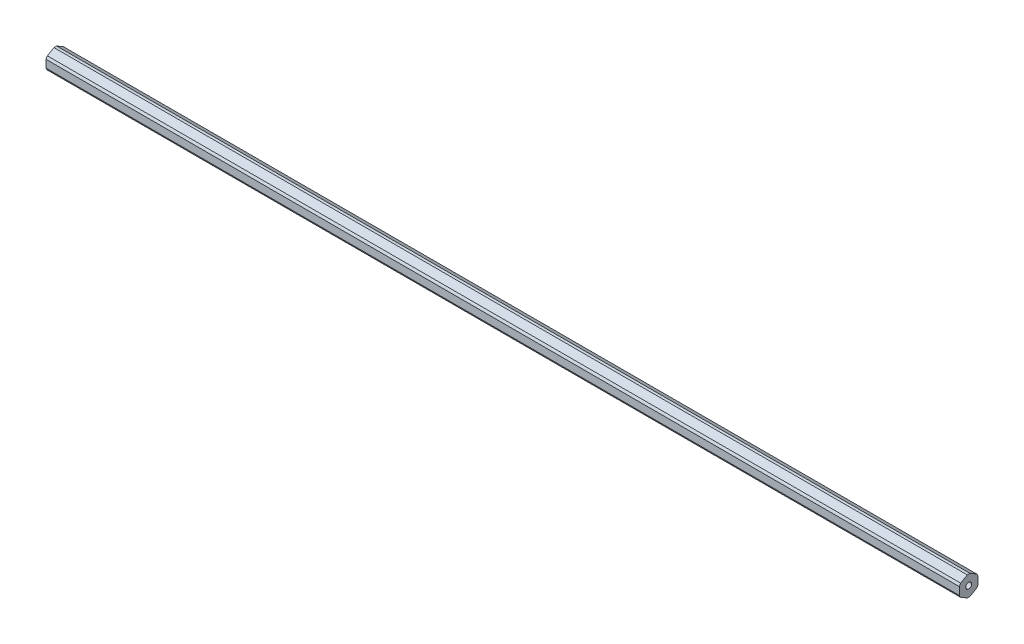
SolidWorks part; units mm, degrees
material "6061 Alloy"
ref_plane "Front Plane" through (0, 0, 0) normal (0, 0, 1) x (1, 0, 0)
ref_plane "Top Plane" through (0, 0, 0) normal (0, 1, 0) x (1, 0, 0)
ref_plane "Right Plane" through (0, 0, 0) normal (1, 0, 0) x (0, 0, -1)
ref_plane "Plane1" through (914.4, 0, 0) normal (1, 0, 0) x (0, 0, -1)
sketch "Sketch1" plane through (914.4, 0, 0) normal (1, 0, 0) x (0, 0, -1)
  line L0 (-5.4343, -4.1949) -> (-0.9157, -6.8037)
  line L1 (0.9157, -6.8037) -> (5.4343, -4.1949)
  line L2 (6.35, -2.6088) -> (6.35, 2.6088)
  line L3 (5.4343, 4.1949) -> (0.9157, 6.8037)
  line L4 (-0.9157, 6.8037) -> (-5.4343, 4.1949)
  line L5 (-6.35, 2.6088) -> (-6.35, -2.6088)
  circle A0 centre (0, 0) radius 1.9939
  arc A1 (-6.35, -2.6088) -> (-5.4343, -4.1949) centre (0, 0) ccw
  arc A2 (-0.9157, -6.8037) -> (0.9157, -6.8037) centre (0, 0) ccw
  arc A3 (5.4343, -4.1949) -> (6.35, -2.6088) centre (0, 0) ccw
  arc A4 (6.35, 2.6088) -> (5.4343, 4.1949) centre (0, 0) ccw
  arc A5 (0.9157, 6.8037) -> (-0.9157, 6.8037) centre (0, 0) ccw
  arc A6 (-5.4343, 4.1949) -> (-6.35, 2.6088) centre (0, 0) ccw
extrude "Boss-Extrude1" add sketch "Sketch1" against normal mid plane 622.3
equation "\"Hex Length\"= 24in + .5in"
equation "\"D1@Boss-Extrude1\"=\"Hex Length\""
